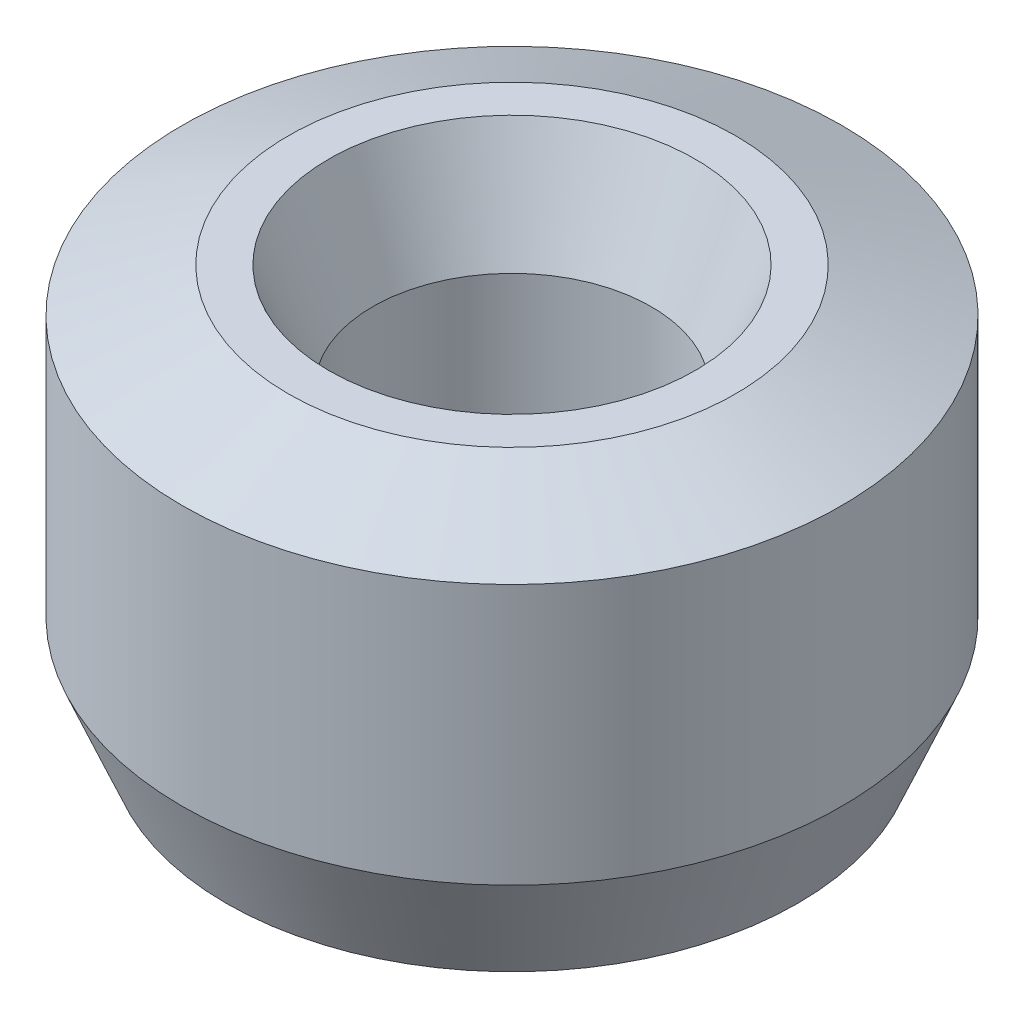
SolidWorks part; units mm, degrees
ref_plane "Front Plane" through (0, 0, 0) normal (0, 0, 1) x (1, 0, 0)
ref_plane "Top Plane" through (0, 0, 0) normal (0, 1, 0) x (1, 0, 0)
ref_plane "Right Plane" through (0, 0, 0) normal (1, 0, 0) x (0, 0, -1)
sketch "Sketch1" plane through (0, 0, 0) normal (0, 1, 0) x (1, 0, 0)
  circle A0 centre (0, 0) radius 25
  dimension "SLEEVE_OD" = 50
extrude "Boss-Extrude1" add sketch "Sketch1" along normal blind 31.1191
sketch "Sketch2" plane through (0, 0, 0) normal (0, 1, 0) x (1, 0, 0)
  circle A0 centre (0, 0) radius 10.5724
  dimension "BORE_D" = 21.1448
extrude "Cut-Extrude1" cut sketch "Sketch2" along normal through all
chamfer "Chamfer1" distance 3.3269 angle 67.51 4 edges at (0, 31.1191, 10.5724) (0, 0, 10.5724) (0, 0, 25) (0, 31.1191, 25) first distance on face at (0, 31.1191, 10.5724) first distance on face at (0, 0, 10.5724) first distance on face at (0, 31.1191, 25)
